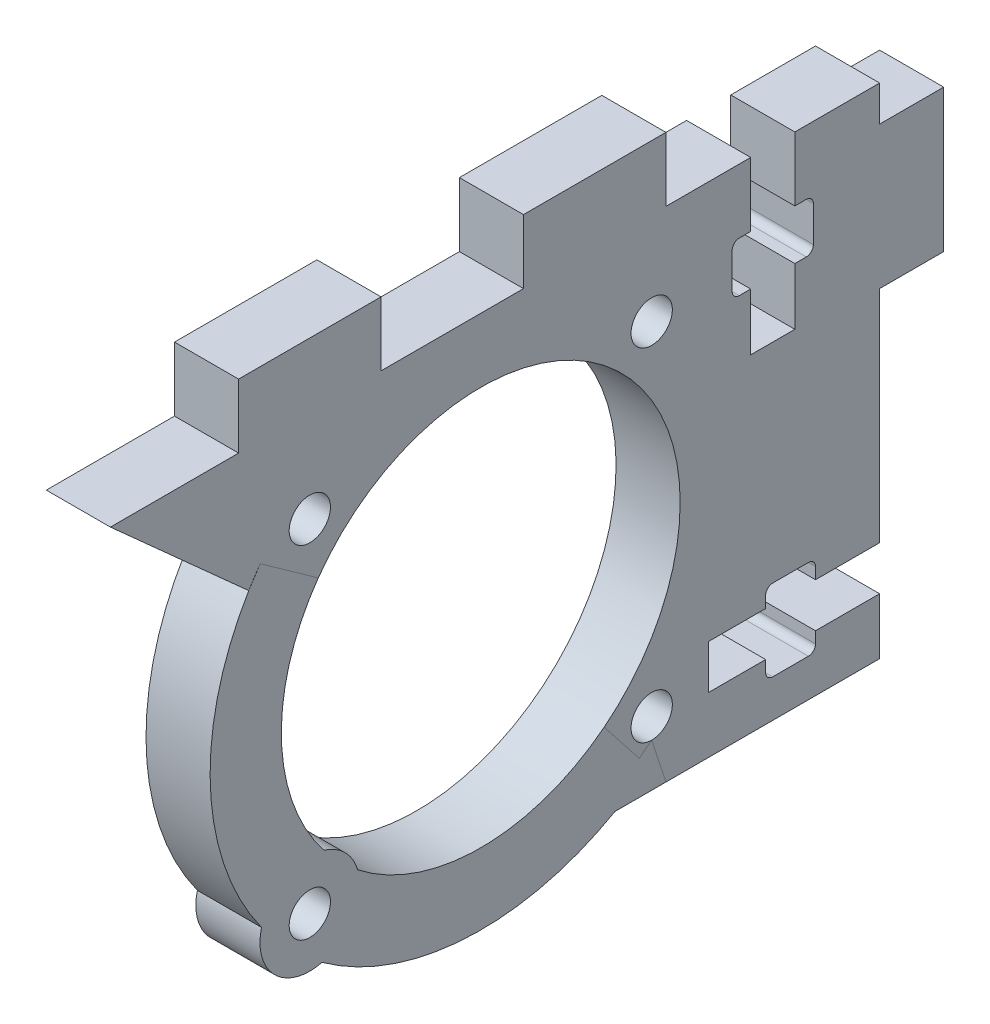
SolidWorks part; units mm, degrees
ref_plane "Front Plane" through (0, 0, 0) normal (0, 0, 1) x (1, 0, 0)
ref_plane "Top Plane" through (0, 0, 0) normal (0, 1, 0) x (1, 0, 0)
ref_plane "Right Plane" through (0, 0, 0) normal (1, 0, 0) x (0, 0, -1)
sketch "Sketch1" plane through (0, 0, 0) normal (1, 0, 0) x (0, 0, -1)
  line L0 (0, 0) -> (0, -35)
  line L1 (0, -35) -> (-54, 0)
  line L2 (-54, 0) -> (0, 0)
  dimension "D1" = 35
  dimension "D2" = 54
extrude "Boss-Extrude1" add sketch "Sketch1" along normal blind 4.5
sketch "Sketch2" plane through (4.5, 0, 0) normal (1, 0, 0) x (0, 0, -1)
  line L0 (0, -35) -> (0, 0) construction
  line L1 (-4.5, -2.5) -> (4.5, -2.5)
  line L2 (-4.5, -2.5) -> (-4.5, -12.5)
  line L3 (-4.5, -12.5) -> (4.5, -12.5)
  line L4 (4.5, -2.5) -> (4.5, -12.5)
  line L5 (-4.5, -2.5) -> (4.5, -12.5) construction
  line L6 (-4.5, -12.5) -> (4.5, -2.5) construction
  line L7 (0, 0) -> (-54, 0) construction
  point P0 (0, -7.5)
  dimension "D1" = 10
  dimension "D2" = 7.5
  dimension "D3" = 4.5
extrude "Boss-Extrude2" add sketch "Sketch2" against normal through all
sketch "Sketch3" plane through (4.5, 0, 0) normal (1, 0, 0) x (0, 0, -1)
  line L0 (0, -35) -> (-15, -35)
  line L1 (0, -25) -> (-54, 0)
  line L4 (0, -35) -> (0, -12.5) construction
  line L5 (0, -25) -> (0, -35)
  line L6 (-54, 0) -> (-15, -35)
  dimension "D1" = 15
  dimension "D2" = 10
extrude "Boss-Extrude3" add sketch "Sketch3" against normal through all
sketch "Sketch4" plane through (4.5, 0, 0) normal (1, 0, 0) x (0, 0, -1)
  line L0 (0, -29.5) -> (-12, -29.5) construction
  line L1 (0, -35) -> (0, -12.5) construction
  line L2 (0, -27.95) -> (-12, -27.95) construction
  line L3 (-12, -27.95) -> (-12, -31.05) construction
  line L4 (0, -31.05) -> (0, -27.95)
  line L5 (0, -27.95) -> (-4.5, -27.95)
  line L6 (-4.5, -27.95) -> (-4.5, -27.15)
  line L7 (-5, -26.65) -> (-7.5, -26.65)
  line L8 (-8, -27.15) -> (-8, -27.95)
  line L9 (-8, -27.95) -> (-12, -27.95)
  line L10 (-12, -27.95) -> (-12, -31.05)
  line L12 (0, -31.05) -> (-12, -31.05) construction
  line L13 (-8, -31.05) -> (-12, -31.05)
  line L14 (-8, -31.85) -> (-8, -31.05)
  line L15 (-5, -32.35) -> (-7.5, -32.35)
  line L16 (-4.5, -31.05) -> (-4.5, -31.85)
  line L17 (0, -31.05) -> (-4.5, -31.05)
  line L18 (4.5, -12.5) -> (4.5, -2.5) construction
  line L19 (0, -18.5) -> (-33.3857, -18.5) construction
  line L20 (-54, 0) -> (-15, -35) construction
  line L37 (0, -31.05) -> (-12, -31.05) construction
  arc A0 (-8, -31.85) -> (-7.5, -32.35) centre (-7.5, -31.85) ccw
  arc A1 (-5, -32.35) -> (-4.5, -31.85) centre (-5, -31.85) ccw
  arc A2 (-4.5, -27.15) -> (-5, -26.65) centre (-5, -27.15) ccw
  arc A3 (-7.5, -26.65) -> (-8, -27.15) centre (-7.5, -27.15) ccw
  point P10 (4.5, -7.5)
  point P20 (-8, -32.35)
  point P23 (-4.5, -32.35)
  point P26 (-4.5, -26.65)
  point P29 (-8, -26.65)
  dimension "D7" = 0.5
  dimension "D1" = 12
  dimension "D2" = 1.55
  dimension "D3" = 2.85
  dimension "D4" = 3.5
  dimension "D5" = 8
  dimension "D6" = 22
extrude "Cut-Extrude1" cut sketch "Sketch4" against normal through all
sketch "Sketch5" plane through (4.5, 0, 0) normal (1, 0, 0) x (0, 0, -1)
  line L0 (0, 0) -> (-54, 0) construction
  line L1 (-25, 4.5) -> (-15, 4.5)
  line L2 (-25, 4.5) -> (-25, 0)
  line L3 (0, 0) -> (-54, 0) construction
  line L4 (-15, 4.5) -> (-15, 0)
  line L5 (-25, 4.5) -> (-20, 0) construction
  line L6 (-20, 0) -> (-15, 4.5) construction
  line L7 (-30, 0) -> (-30, 4.5) construction
  line L8 (-40, 0) -> (-45, 4.5) construction
  line L9 (-35, 4.5) -> (-40, 0) construction
  line L10 (-45, 4.5) -> (-45, 0)
  line L12 (-35, 4.5) -> (-35, 0)
  line L13 (-35, 4.5) -> (-45, 4.5)
  line L14 (-20, 0) -> (-15, 4.5) construction
  line L15 (-15, 0) -> (-25, 0)
  line L16 (-35, 0) -> (-45, 0)
  point P0 (-20, 0)
  point P14 (-40, 0)
  dimension "D3" = 4.5
  dimension "D1" = 20
  dimension "D2" = 10
  dimension "D4" = 20
  dimension "D5" = 5
extrude "Boss-Extrude4" add sketch "Sketch5" against normal through all
sketch "Sketch8" [suppressed] plane through (4.5, 0, 0) normal (1, 0, 0) x (0, 0, -1)
  line L0 (-15, -30) -> (-27, -30) construction
  line L1 (-15, -35) -> (-27, -35)
  line L2 (-15, -25) -> (-27, -25)
  line L3 (-15, -35) -> (0, -35) construction
  line L4 (-15, -25) -> (-15, -35)
  arc A1 (-27, -25) -> (-27, -35) centre (-27, -30) ccw
  dimension "D5" = 5
  dimension "D1" = 0
  dimension "D2" = 12
  dimension "D3" = 0
  dimension "D4" = 10
extrude "Boss-Extrude5" [suppressed] add sketch "Sketch8" against normal up to surface (4.5 mm away) up to face at (0, -17.3125, 11.9375)
sketch "Sketch9" [suppressed] plane through (4.5, 0, 0) normal (1, 0, 0) x (0, 0, -1)
  line L0 (-27, -30) -> (-22, -30) construction
  line L1 (-27, -27) -> (-22, -27)
  line L2 (-27, -33) -> (-22, -33)
  arc A0 (-27, -27) -> (-27, -33) centre (-27, -30) ccw
  arc A1 (-22, -33) -> (-22, -27) centre (-22, -30) ccw
  point P3 (-24.5, -30)
  dimension "D1" = 3
  dimension "D2" = 5
extrude "Cut-Extrude3" [suppressed] cut sketch "Sketch9" against normal through all
sketch "Sketch10" plane through (0, 0, 0) normal (-1, 0, 0) x (0, 0, 1)
  line L0 (15, -35) -> (54, -12)
  line L1 (54, -12) -> (54, 0)
  line L3 (54, 0) -> (15, -35)
  dimension "D1" = 12
extrude "Boss-Extrude6" [suppressed] add sketch "Sketch10" against normal through all
sketch "Sketch6" plane through (4.5, 0, 0) normal (1, 0, 0) x (0, 0, -1)
  line L0 (-30, 0) -> (-30, -11) construction
  line L1 (-25, 0) -> (-35, 0) construction
  line L2 (-28.45, -11) -> (-31.55, -11) construction
  line L3 (-31.55, -11) -> (-31.55, 0) construction
  line L4 (-28.45, 0) -> (-31.55, 0)
  line L5 (-31.55, 0) -> (-31.55, -4.5)
  line L6 (-31.55, -4.5) -> (-32.35, -4.5)
  line L7 (-32.85, -5) -> (-32.85, -7.5)
  line L8 (-32.35, -8) -> (-31.55, -8)
  line L9 (-31.55, -8) -> (-31.55, -11)
  line L10 (-31.55, -11) -> (-28.45, -11)
  line L11 (-28.45, -11) -> (-28.45, 0) construction
  line L12 (-28.45, -8) -> (-28.45, -11)
  line L13 (-27.65, -8) -> (-28.45, -8)
  line L14 (-27.15, -5) -> (-27.15, -7.5)
  line L15 (-28.45, -4.5) -> (-27.65, -4.5)
  line L16 (-28.45, 0) -> (-28.45, -4.5)
  arc A0 (-32.85, -7.5) -> (-32.35, -8) centre (-32.35, -7.5) ccw
  arc A1 (-32.35, -4.5) -> (-32.85, -5) centre (-32.35, -5) ccw
  arc A2 (-27.65, -4.5) -> (-27.15, -5) centre (-27.65, -5) cw
  arc A3 (-27.15, -7.5) -> (-27.65, -8) centre (-27.65, -7.5) cw
  point P12 (-32.85, -8)
  point P15 (-32.85, -4.5)
  point P26 (-27.15, -4.5)
  point P27 (-27.15, -8)
  dimension "D2" = 1.55
  dimension "D4" = 3.5
  dimension "D6" = 0.5
  dimension "D1" = 11
  dimension "D3" = 8
  dimension "D5" = 2.85
extrude "Cut-Extrude2" [suppressed] cut sketch "Sketch6" against normal through all
sketch "Sketch11" plane through (0, 0, 0) normal (-1, 0, 0) x (0, 0, 1)
  line L0 (7.5, 0) -> (7.5, -12) construction
  line L1 (0, 0) -> (15, 0) construction
  line L2 (5.95, -12) -> (9.05, -12)
  line L3 (9.05, -12) -> (9.05, -8)
  line L4 (9.05, -8) -> (9.85, -8)
  line L5 (10.35, -7.5) -> (10.35, -5)
  line L6 (9.85, -4.5) -> (9.05, -4.5)
  line L7 (9.05, -4.5) -> (9.05, 0)
  line L8 (9.05, 0) -> (5.95, 0)
  line L9 (9.05, -8) -> (9.05, -4.5) construction
  line L10 (0, 0) -> (15, 0) construction
  line L11 (5.95, -8) -> (5.95, -4.5) construction
  line L12 (5.95, -4.5) -> (5.95, 0)
  line L13 (5.15, -4.5) -> (5.95, -4.5)
  line L14 (4.65, -7.5) -> (4.65, -5)
  line L15 (5.95, -8) -> (5.15, -8)
  line L16 (5.95, -12) -> (5.95, -8)
  arc A0 (10.35, -5) -> (9.85, -4.5) centre (9.85, -5) ccw
  arc A1 (5.15, -4.5) -> (4.65, -5) centre (5.15, -5) ccw
  arc A2 (9.85, -8) -> (10.35, -7.5) centre (9.85, -7.5) ccw
  arc A3 (4.65, -7.5) -> (5.15, -8) centre (5.15, -7.5) ccw
  point P11 (7.5, 0)
  point P22 (10.35, -4.5)
  point P25 (4.65, -4.5)
  point P28 (10.35, -8)
  point P31 (4.65, -8)
  dimension "D7" = 0.5
  dimension "D1" = 12
  dimension "D3" = 2.85
  dimension "D8" = 0.5
  dimension "D2" = 3.5
  dimension "D4" = 8
  dimension "D5" = 1.55
  dimension "D6" = 0
extrude "Cut-Extrude4" cut sketch "Sketch11" against normal through all
sketch "Sketch12" plane through (0, 0, 0) normal (-1, 0, 0) x (0, 0, 1)
  line L0 (28, -18.5) -> (16, -6.5) construction
  line L1 (28, -18.5) -> (28, -4.5) construction
  line L2 (28, -18.5) -> (40, -6.5) construction
  line L3 (28, -18.5) -> (14, -18.5) construction
  line L4 (28, -18.5) -> (16, -30.5) construction
  line L5 (28, -18.5) -> (16, -6.5) construction
  line L6 (0, -27.95) -> (0, -12.5) construction
  line L7 (25, 0) -> (35, 0) construction
  circle A0 centre (28, -18.5) radius 14
  circle A1 centre (16, -6.5) radius 1.45
  circle A2 centre (40, -6.5) radius 1.45
  circle A3 centre (16, -30.5) radius 1.45
  dimension "D1" = 28
  dimension "D2" = 2.9
  dimension "D3" = 12
  dimension "D4" = 45
  dimension "D5" = 28
  dimension "D6" = 18.5
extrude "FanCutout" cut sketch "Sketch12" against normal through all
sketch "Sketch13" plane through (0, 0, 0) normal (-1, 0, 0) x (0, 0, 1)
  line L0 (39.4071, -10.3834) -> (43.481, -7.4847)
  line L1 (19.3358, -29.4969) -> (16.2414, -33.4243)
  line L6 (28, -18.5) -> (54, 0) construction
  line L7 (28, -18.5) -> (15, -35) construction
  arc A0 (19.3358, -29.4969) -> (39.4071, -10.3834) centre (28, -18.5) ccw
  arc A1 (16.2414, -33.4243) -> (43.481, -7.4847) centre (28, -18.5) ccw
  arc A3 (40.4722, -12.1404) -> (20.333, -30.214) centre (28, -18.5) ccw construction
  dimension "D1" = 5
extrude "Boss-Extrude7" add sketch "Sketch13" against normal through all
sketch "Sketch14" plane through (0, 0, 0) normal (-1, 0, 0) x (0, 0, 1)
  line L0 (28, -4.5) -> (28, -32.5) construction
  line L1 (28, -18.5) -> (40, -30.5) construction
  circle A0 centre (28, -18.5) radius 14 construction
  circle A1 centre (40, -30.5) radius 3.5
  dimension "D2" = 7
  dimension "D1" = 45
  dimension "D3" = 12
extrude "Boss-Extrude8" add sketch "Sketch14" against normal through all
sketch "Sketch15" plane through (0, 0, 0) normal (-1, 0, 0) x (0, 0, 1)
  line L0 (42.4749, -32.9749) -> (28, -18.5) construction
  arc A0 (39.1388, -33.8924) -> (43.3924, -29.6388) centre (40, -30.5) ccw construction
  circle A1 centre (40, -30.5) radius 1.45
  dimension "D1" = 2.9
extrude "Cut-Extrude6" cut sketch "Sketch15" against normal through all
sketch "Sketch16" [suppressed] plane through (4.5, 0, 0) normal (1, 0, 0) x (0, 0, -1)
  line L0 (0, -34.5) -> (-39, -34.5) construction
  line L1 (0, -27.95) -> (0, -12.5) construction
  line L2 (-15, -34.5) -> (-39, -34.5) construction
  line L3 (-15, -38.5) -> (-39, -38.5)
  line L4 (-15, -30.5) -> (-39, -30.5)
  arc A0 (-15, -38.5) -> (-15, -30.5) centre (-15, -34.5) ccw
  arc A1 (-39, -30.5) -> (-39, -38.5) centre (-39, -34.5) ccw
  point P5 (-27, -34.5)
  point P12 (0, -20.225)
  dimension "D1" = 4
  dimension "D2" = 34.5
  dimension "D3" = 39
  dimension "D4" = 15
extrude "Boss-Extrude9" [suppressed] add sketch "Sketch16" against normal through all
sketch "Sketch17" [suppressed] plane through (4.5, 0, 0) normal (1, 0, 0) x (0, 0, -1)
  line L0 (-43, -34.5) -> (0, -34.5) construction
  line L1 (0, -27.75) -> (0, -12.5) construction
  line L2 (-26.5, -34.5) -> (-26.5, -20.0064) construction
  arc A0 (-42.1823, -32.0766) -> (-39, -38.5) centre (-39, -34.5) ccw construction
  circle A1 centre (-39, -34.5) radius 1.55
  circle A2 centre (-14, -34.5) radius 1.55
  dimension "D1" = 2.9
  dimension "D2" = 12.5
extrude "Cut-Extrude7" [suppressed] cut sketch "Sketch17" against normal through all
sketch "Sketch18" [suppressed] plane through (4.5, 0, 0) normal (1, 0, 0) x (0, 0, -1)
  line L0 (-15, -38.5) -> (0, -35)
  line L1 (0, -35) -> (-11.0314, -35)
  line L2 (-11.0314, -35) -> (-15, -38.5)
extrude "Boss-Extrude10" [suppressed] add sketch "Sketch18" against normal through all
sketch "Sketch20" [suppressed] plane through (4.5, 0, 0) normal (1, 0, 0) x (0, 0, -1)
  line L0 (0, -35) -> (0, -31.05) construction
  line L1 (-9, -38) -> (-37.9081, -38)
  line L2 (-40.7232, -36.0371) -> (-54, 0)
  line L3 (-54, 0) -> (-15, -35)
  line L4 (-15, -35) -> (-6, -35)
  line L5 (-9, -38) -> (-6, -35)
  line L6 (-40.7232, -36.0371) -> (-40, -38) construction
  line L7 (-40, -38) -> (-37.9081, -38) construction
  arc A1 (-37.9081, -38) -> (-40.7232, -36.0371) centre (-37.9081, -35) cw
  point P0 (0, -33.025)
  point P14 (-40, -38)
  dimension "D3" = 6
  dimension "D4" = 3
  dimension "D1" = 40
  dimension "D2" = 3
  dimension "D5" = 135
extrude "Boss-Extrude11" [suppressed] add sketch "Sketch20" against normal through all
sketch "Sketch21" [suppressed] plane through (4.5, 0, 0) normal (1, 0, 0) x (0, 0, -1)
  line L0 (0, -34.5) -> (-41.2895, -34.5) construction
  line L1 (0, -35) -> (0, -31.05) construction
  line L2 (-54, 0) -> (-40.7232, -36.0371) construction
  line L3 (0, -27.95) -> (0, -12.5) construction
  circle A0 centre (-36, -34.5) radius 1.45
  circle A1 centre (-11, -34.5) radius 1.45
  dimension "D2" = 2.9
  dimension "D3" = 2.9
  dimension "D1" = 25
  dimension "D4" = 34.5
  dimension "D5" = 11
extrude "Cut-Extrude8" [suppressed] cut sketch "Sketch21" against normal through all
sketch "Sketch22" [suppressed] plane through (4.5, 0, 0) normal (1, 0, 0) x (0, 0, -1)
  line L0 (0, -27.95) -> (0, -12.5) construction
  line L1 (-25, 0) -> (-35, 0) construction
  circle A0 centre (-28, -18) radius 13.25
  dimension "D2" = 18
  dimension "D3" = 26.5
  dimension "D1" = 28
extrude "Cut-Extrude9" [suppressed] cut sketch "Sketch22" against normal through all
sketch "Sketch24" plane through (0, 0, 0) normal (-1, 0, 0) x (0, 0, 1)
  line L0 (15, -35) -> (20, -35)
  line L1 (20, -35) -> (16, -31.95)
  line L2 (16, -31.95) -> (15, -35)
  circle A0 centre (16, -30.5) radius 1.45 construction
  dimension "D1" = 5
extrude "Boss-Extrude13" add sketch "Sketch24" against normal through all
equation "\"X-ROD-SPACING\"=45"
equation "\"Y-ROD-SPACING\"=75"
equation "\"Z-ROD-SPACING\"=17.5"
equation "\"Y-BED-OFFSET\"=2"
equation "\"Y-BED-ROD-INSET\"=3.5"
equation "\"Y-BED-SCREW-SPACING\"=209"
equation "\"Y-BED-SCREW-CUTOUT-SLOT-HEIGHT\"=2"
equation "\"T-SLOT-NUT-FILLET-RADIUS\"=0.5"
equation "\"T-SLOT-SCREW-SHAFT-RADIUS\"=1.55"
equation "\"T-SLOT-SCREW-SHAFT-CUTOUT-LENGTH\"=11.0"
equation "\"T-SLOT-NUT-DEPTH\"=3.5"
equation "\"T-SLOT-NUT-WIDTH\"=2.85"
equation "\"T-SLOT-NUT-END-DISTANCE\"=8"
equation "\"ACRYLIC-THICKNESS\"=10"
equation "\"ACRYLIC-THICKNESS2\"=4.5"
equation "\"ACRYLIC-TAB-CUTOUT-SIZE\"=\"ACRYLIC-THICKNESS\"+\"ACRYLIC-TAB-TOLERANCE\"*2"
equation "\"ACRYLIC-TAB-WIDTH\"=\"ACRYLIC-THICKNESS\""
equation "\"ACRYLIC-M3-HOLE\"=2.9"
equation "\"SMOOTHROD-CAP-SCREW-DISTANCE\"=20"
equation "\"FRAME-WIDTH-INNER\"=370"
equation "\"NEMA17-HOLE-SPACING\"=31"
equation "\"NEMA17-CENTRAL-CUTOUT\"=22.5"
equation "\"Z-BRACKET-REACH\"=55"
equation "\"Z-ROD-INSET\"=16"
equation "\"TOP-BRACKET-SPACING\"=40"
equation "\"SMOOTHROD-X-LENGTH\"=350"
equation "\"SMOOTHROD-Y-LENGTH\"=350"
equation "\"SMOOTHROD-Z-LENGTH\"=350"
equation "\"SMOOTHROD-TIGHTENING-HEADROOM\"=.25"
equation "\"LEADSCREW-Z-LENGTH\"=300"
equation "\"SCREW-LENGTH-FRAME\"=\"ACRYLIC-THICKNESS\" + 10"
equation "\"SCREW-LENGTH-MOTOR\"=\"ACRYLIC-THICKNESS\" + 5"
equation "\"SCREW-LENGTH-EXTRUDER\"=28"
equation "\"SCREW-HEAD-RADIUS\"=6"
equation "\"PRINTED-X-SMOOTHROD-DIAMETER\"=9.0"
equation "\"PRINTED-X-SMOOTHROD-CUTOUT\"=10"
equation "\"PRINTED-X-BASE-HEIGHT\"=10"
equation "\"PRINTED-LM8UU-CUTOUT-SIZE\"=15.5"
equation "\"PRINTED-LM8UU-CUTOUT-LENGTH\"=24.5"
equation "\"PRINTED-X-IDLER-HEIGHT\"=16"
equation "\"PSU-MOUNTING-WIDTH\"=95"
equation "\"PSU-MOUNTING-HEIGHT\"=177"
equation "\"Y-BELT-TO-ROD-DISTANCE\"=20"
equation "\"SPOOL-HOLDER-ROD-SPACING\"=150"
equation "\"ACRYLIC-X-CARRIAGE-WIDTH\"=55"
equation "\"ACRYLIC-X-CARRIAGE-HEIGHT\"=75"
equation "\"ACRYLIC-X-CARRIAGE-SCREW-SPACING-X\"=15"
equation "\"ACRYLIC-X-CARRIAGE-SCREW-SPACING-Y\"=33"
equation "\"ACRYLIC-X-CARRIAGE-CENTER-TAB-SPACING\"=14"
equation "\"ACRYLIC-X-CARRIAGE-EXTRUDER-SHELF-DEPTH\"=\"ACRYLIC-X-CARRIAGE-EXTRUDER-OFFSET\" + 28"
equation "\"D2@Sketch1\"=\"ACRYLIC-X-CARRIAGE-EXTRUDER-SHELF-DEPTH\""
equation "\"D1@Boss-Extrude1\"=\"ACRYLIC-THICKNESS2\""
equation "\"D1@Sketch2\"=\"ACRYLIC-TAB-WIDTH\""
equation "\"D3@Sketch2\"=\"ACRYLIC-THICKNESS2\""
equation "\"ACRYLIC-X-CARRIAGE-LM8UU-CUTOUT-WIDTH\"=24.25"
equation "\"ACRYLIC-X-CARRIAGE-EXTRUDER-BRACE-SPACING\"=23"
equation "\"ACRYLIC-X-CARRIAGE-EXTRUDER-BRACE-HEIGHT\"=35"
equation "\"D1@Sketch1\"=\"ACRYLIC-X-CARRIAGE-EXTRUDER-BRACE-HEIGHT\""
equation "\"D1@Sketch4\"=\"T-SLOT-SCREW-SHAFT-CUTOUT-LENGTH\"+1"
equation "\"D2@Sketch4\"=\"T-SLOT-SCREW-SHAFT-RADIUS\""
equation "\"D3@Sketch4\"=\"T-SLOT-NUT-WIDTH\""
equation "\"D4@Sketch4\"=\"T-SLOT-NUT-DEPTH\""
equation "\"D5@Sketch4\"=\"T-SLOT-NUT-END-DISTANCE\""
equation "\"D7@Sketch4\"=\"T-SLOT-NUT-FILLET-RADIUS\""
equation "\"ACRYLIC-X-CARRIAGE-EXTRUDER-BRACE-SCREW-SPACING\"=22"
equation "\"D6@Sketch4\"=\"ACRYLIC-X-CARRIAGE-EXTRUDER-BRACE-SCREW-SPACING\""
equation "\"ACRYLIC-X-CARRIAGE-EXTRUDER-BRACE-TAB-OFFSET\"=20"
equation "\"D1@Sketch5\"=\"ACRYLIC-X-CARRIAGE-EXTRUDER-BRACE-TAB-OFFSET\""
equation "\"D2@Sketch5\"=\"ACRYLIC-TAB-WIDTH\""
equation "\"D3@Sketch5\"=\"ACRYLIC-THICKNESS2\""
equation "\"ACRYLIC-X-CARRIAGE-EXTRUDER-OFFSET\"=26"
equation "\"ACRYLIC-X-CARRIAGE-EXTRUDER-ANGLE\"=90"
equation "\"D1@Sketch6\"=\"T-SLOT-SCREW-SHAFT-CUTOUT-LENGTH\""
equation "\"D2@Sketch6\"=\"T-SLOT-SCREW-SHAFT-RADIUS\""
equation "\"D3@Sketch6\"=\"T-SLOT-NUT-END-DISTANCE\""
equation "\"D4@Sketch6\"=\"T-SLOT-NUT-DEPTH\""
equation "\"D5@Sketch6\"=\"T-SLOT-NUT-WIDTH\""
equation "\"D6@Sketch6\"=\"T-SLOT-NUT-FILLET-RADIUS\""
equation "\"D1@Sketch11\"=\"T-SLOT-SCREW-SHAFT-CUTOUT-LENGTH\"+1"
equation "\"D2@Sketch11\"=\"T-SLOT-NUT-DEPTH\""
equation "\"D3@Sketch11\"=\"T-SLOT-NUT-WIDTH\""
equation "\"D4@Sketch11\"=\"T-SLOT-NUT-END-DISTANCE\""
equation "\"D5@Sketch11\"=\"T-SLOT-SCREW-SHAFT-RADIUS\""
equation "\"D7@Sketch11\"=\"T-SLOT-NUT-FILLET-RADIUS\""
equation "\"D8@Sketch11\"=\"T-SLOT-NUT-FILLET-RADIUS\""
equation "\"D2@Sketch12\"=\"ACRYLIC-M3-HOLE\""
equation "\"D1@Sketch15\"=\"ACRYLIC-M3-HOLE\""
equation "\"D1@Sketch17\"=\"ACRYLIC-M3-HOLE\""
equation "\"D2@Sketch21\"=\"ACRYLIC-M3-HOLE\""
equation "\"D3@Sketch21\"=\"ACRYLIC-M3-HOLE\""
